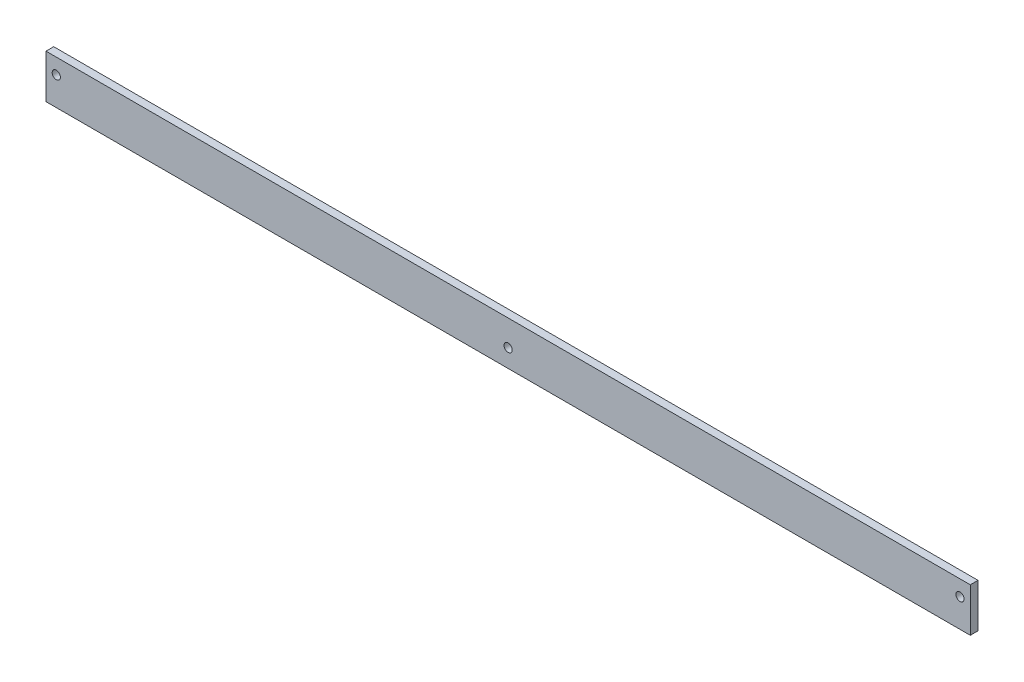
SolidWorks part; units mm, degrees
ref_plane "Plan de face" through (0, 0, 0) normal (0, 0, 1) x (1, 0, 0)
ref_plane "Plan de dessus" through (0, 0, 0) normal (0, 1, 0) x (1, 0, 0)
ref_plane "Plan de droite" through (0, 0, 0) normal (1, 0, 0) x (0, 0, -1)
sketch "Esquisse1" plane through (0, 0, 0) normal (0, 0, 1) x (1, 0, 0)
  line L1 (259.5, -8.5) -> (-99.5, -8.5)
  line L2 (259.5, -8.5) -> (259.5, 8.5)
  line L3 (259.5, 8.5) -> (-99.5, 8.5)
  line L4 (-99.5, -8.5) -> (-99.5, 8.5)
  line L5 (259.5, -11.5) -> (259.5, -8.5) construction
  point P0 (0, 0)
  dimension "D2" = 17
extrude "Boss.-Extru.1" add sketch "Esquisse1" along normal blind 3
sketch "Sketch1" plane through (0, 0, 0) normal (0, 0, -1) x (-1, 0, 0)
  circle A0 centre (95.5, 2.5) radius 1.6
  point P3 (95.5126, 2.6795)
  point P4 (95.5, 2.5)
extrude "Cut-Extrude1" cut sketch "Sketch1" against normal through all
sketch "Sketch2" plane through (0, 0, 0) normal (0, 0, -1) x (-1, 0, 0)
  circle A0 centre (-255.5, 2.5) radius 1.6
extrude "Cut-Extrude2" cut sketch "Sketch2" against normal through all
sketch "Sketch3" plane through (0, 0, 0) normal (0, 0, -1) x (-1, 0, 0)
  circle A0 centre (-80, -1.5) radius 1.6
extrude "Cut-Extrude3" cut sketch "Sketch3" against normal through all
